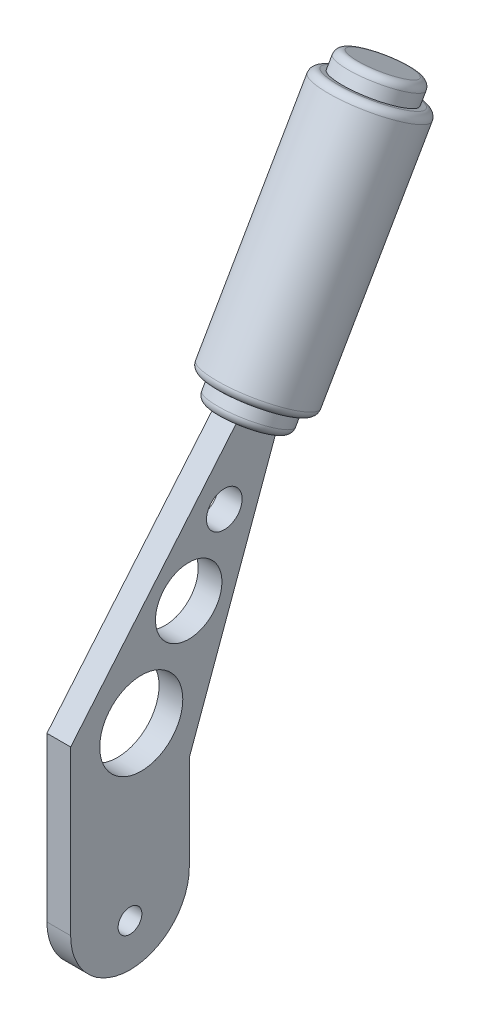
SolidWorks part; units mm, degrees
ref_plane "Płaszczyzna przednia" through (0, 0, 0) normal (0, 0, 1) x (1, 0, 0)
ref_plane "Płaszczyzna górna" through (0, 0, 0) normal (0, 1, 0) x (1, 0, 0)
ref_plane "Płaszczyzna prawa" through (0, 0, 0) normal (1, 0, 0) x (0, 0, -1)
sketch "Szkic1" plane through (0, 0, 0) normal (1, 0, 0) x (0, 0, -1)
  line L0 (-25, 0) -> (-25, 68.8675)
  line L1 (25, 0) -> (25, 40)
  line L2 (-25, 68.8675) -> (44.8412, 152.1011)
  line L3 (44.8412, 152.1011) -> (62.1617, 142.1011)
  line L4 (62.1617, 142.1011) -> (25, 40)
  line L5 (25, 40) -> (-37.6022, 76.1434) construction
  line L6 (-3.9985, 47.5081) -> (53.5015, 147.1011) construction
  line L7 (25, 40) -> (-25, 40) construction
  arc A0 (25, 0) -> (-25, 0) centre (0, 0) cw
  circle A1 centre (39.7515, 123.2854) radius 7.5
  circle A2 centre (24.7515, 97.3046) radius 14
  circle A3 centre (4.7515, 62.6636) radius 17.5
  circle A4 centre (0, -7) radius 5
  point P18 (0, -25)
  point P19 (21.2019, 94.0433)
  point P20 (8.0037, 71.1833)
  point P21 (11.3011, 74.641)
  dimension "D1" = 25
  dimension "D6" = 28
  dimension "D7" = 30
  dimension "D8" = 15
  dimension "D10" = 35
  dimension "D11" = 10
  dimension "D2" = 20
  dimension "D3" = 40
  dimension "D4" = 80
  dimension "D5" = 80
  dimension "D9" = 40
  dimension "D12" = 18
  dimension "D13" = 30
extrude "Dodanie-wyciągnięcie1" add sketch "Szkic1" along normal blind 5 and the other way blind 5
sketch "Szkic3" plane through (0, 0, 0) normal (1, 0, 0) x (0, 0, -1)
  line L0 (53.5015, 147.1011) -> (148.5404, 311.7133) construction
  line L1 (62.1617, 142.1011) -> (44.8412, 152.1011) construction
  line L2 (40.5111, 154.6011) -> (53.5015, 147.1011)
  line L3 (40.5111, 154.6011) -> (44.5111, 161.5293)
  line L4 (44.5111, 161.5293) -> (40.181, 164.0293)
  line L5 (40.181, 164.0293) -> (90.181, 250.6318)
  line L6 (90.181, 250.6318) -> (94.5111, 248.1318)
  line L7 (94.5111, 248.1318) -> (98.5111, 255.06)
  line L8 (98.5111, 255.06) -> (111.5015, 247.56)
  line L9 (111.5015, 247.56) -> (53.5015, 147.1011)
  dimension "D1" = 15
  dimension "D2" = 5
  dimension "D3" = 100
  dimension "D4" = 8
revolve "Obrót1" add sketch "Szkic3" angle 360 about L0
fillet "Zaokrąglenie1" radius 3 2 edges at (0, 240.06, -124.4919) (0, 139.6011, -66.4919)
fillet "Zaokrąglenie2" radius 3 2 edges at (0, 144.0293, -74.822) (0, 230.6318, -124.822)
